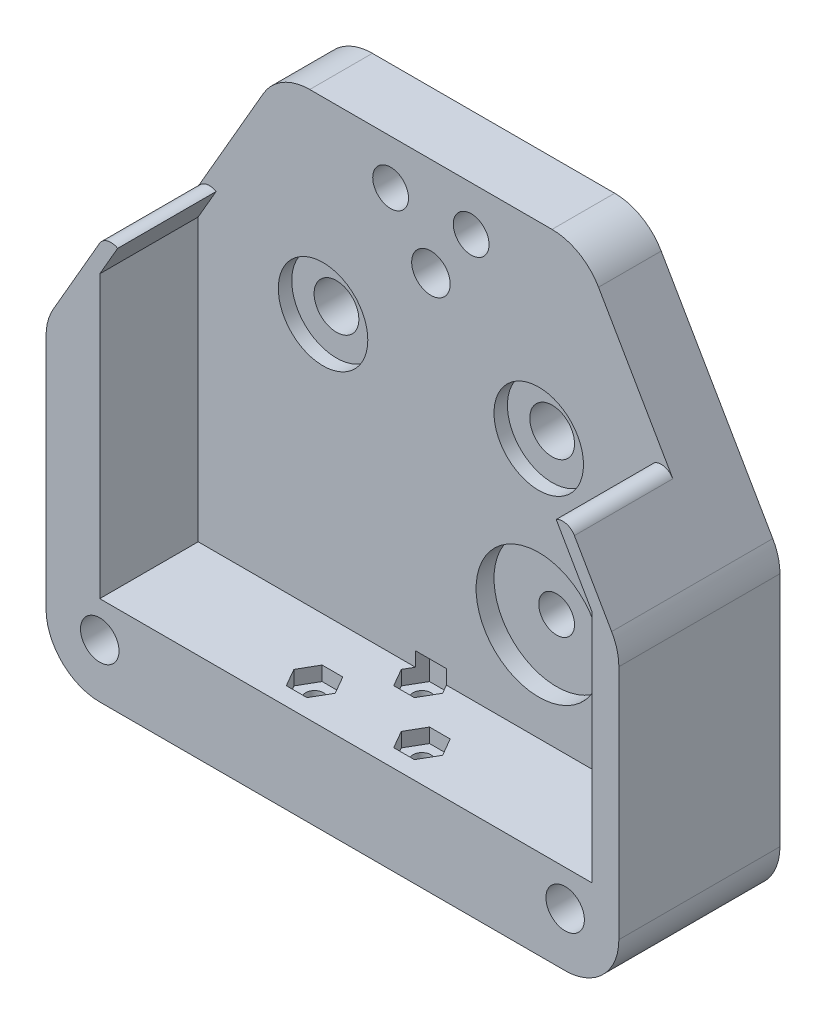
SolidWorks part; units mm, degrees
material "ABS"
ref_plane "Спереди" through (0, 0, 0) normal (0, 0, 1) x (1, 0, 0)
ref_plane "Сверху" through (0, 0, 0) normal (0, 1, 0) x (1, 0, 0)
ref_plane "Справа" through (0, 0, 0) normal (1, 0, 0) x (0, 0, -1)
sketch "Эскиз1" plane through (0, 0, 0) normal (0, 0, 1) x (1, 0, 0)
  line L0 (0, 0) -> (64, 0)
  line L1 (64, 0) -> (64, 34.0192)
  line L2 (64, 34.0192) -> (49, 60)
  line L3 (49, 60) -> (15, 60)
  line L4 (15, 60) -> (0, 34.02)
  line L5 (0, 34.02) -> (0, 0)
  dimension "D1" = 64
  dimension "D2" = 60
  dimension "D3" = 120
  dimension "D4" = 34
  dimension "D5" = 30
  dimension "D6" = 34.02
extrude "Бобышка-Вытянуть1" add sketch "Эскиз1" along normal blind 7
sketch "Эскиз3" plane through (0, 0, 7) normal (0, 0, 1) x (1, 0, 0)
  line L0 (0, 0) -> (64, 0)
  line L1 (64, 0) -> (64, 34.0192)
  line L2 (64, 34.0192) -> (58.2904, 43.9086)
  line L3 (64, 34.0192) -> (49, 60) construction
  line L4 (58.2904, 43.9086) -> (57, 43.1636)
  line L5 (57, 43.1636) -> (61, 36.2354)
  line L6 (61, 36.2354) -> (61, 10)
  line L7 (61, 10) -> (6, 10)
  line L8 (6, 10) -> (6, 41.4321)
  line L9 (6, 41.4321) -> (8, 44.8961)
  line L10 (8, 44.8961) -> (6.7097, 45.6412)
  line L11 (15, 60) -> (0, 34.02) construction
  line L12 (6.7097, 45.6412) -> (0, 34.02)
  line L13 (0, 34.02) -> (0, 0)
  dimension "D1" = 55
  dimension "D2" = 6
  dimension "D3" = 10
  dimension "D4" = 4
  dimension "D5" = 8
  dimension "D6" = 1.49
  dimension "D7" = 1.49
extrude "Бобышка-Вытянуть2" add sketch "Эскиз3" along normal blind 11
fillet "Скругление1" radius 6 6 edges at (64, 34.0192, 9) (49, 60, 3.5) (15, 60, 3.5) (0, 34.02, 9) (0, 0, 9) (64, 0, 9)
fillet "Скругление2" radius 1.49 2 edges at (58.2904, 43.9086, 12.5) (6.7097, 45.6412, 12.5)
hole_wizard "Зенковка для  винта с плоской головкой M44" positions "Эскиз13" profile "Эскиз14" countersink size "M4" standard "Ansi Metric" end condition through all
sketch "Эскиз13" plane through (0, 0, 0) normal (0, 0, -1) x (-1, 0, 0)
  line L3 (-32, 62.7004) -> (-32, -1.1162) construction
  line L5 (-45.5359, 60) -> (-18.4641, 60) construction
  line L6 (-6, 0) -> (-58, 0) construction
  line L7 (-64, 6) -> (-64, 32.4115) construction
  point P0 (-5.9999, 6)
  point P2 (-58, 6)
  point P4 (-32, 49)
  point P34 (-32, 60)
  dimension "D1" = 11
  dimension "D2" = 6
  dimension "D3" = 6
sketch "Эскиз14" plane through (5.9999, 6, 0) normal (1, 0, 0) x (0, 1, 0)
  line L0 (0, 0) -> (0, 18)
  line L1 (0, 18) -> (2.15, 18)
  line L2 (2.15, 18) -> (2.15, 2.2)
  line L3 (2.15, 2.2) -> (4.35, 0)
  line L5 (4.35, 0) -> (0, 0)
  line L6 (-2.15, 2.2) -> (-4.35, 0) construction
  line L11 (0, -3.8306) -> (0, 22.0892) construction
  dimension "Диаметр сквозного отверстия" = 4.3
  dimension "Глубина сквозного отверстия" = 18
  dimension "Диаметр передней зенковки" = 8.7
  dimension "Угол передней зенковки" = 90
hole_wizard "Отверстия под штифты Ø4.0 мм2" positions "Эскиз19" profile "Эскиз20" hole size "Ø4.0" standard "Ansi Metric" end condition through all
sketch "Эскиз19" plane through (0, 0, 0) normal (0, 0, -1) x (-1, 0, 0)
  line L0 (-45.5359, 60) -> (-18.4641, 60) construction
  line L1 (-64, 6) -> (-64, 32.4115) construction
  line L8 (-32, 62.4273) -> (-32, -3.8376) construction
  point P0 (-36.5, 55)
  point P2 (-27.4999, 55)
  point P94 (-32, 60)
  dimension "D1" = 5
  dimension "D2" = 27.5
sketch "Эскиз20" plane through (36.5, 55, 0) normal (1, 0, 0) x (0, 1, 0)
  line L0 (0, 0) -> (0, 18)
  line L1 (0, 18) -> (2, 18)
  line L2 (2, 18) -> (2, 0)
  line L5 (2, 0) -> (0, 0)
  line L11 (0, -3.866) -> (0, 11.4564) construction
  dimension "Диаметр сквозного отверстия" = 4
  dimension "Глубина сквозного отверстия" = 18
hole_wizard "Отверстия под штифты Ø5.0 мм1" positions "Эскиз21" profile "Эскиз22" hole size "Ø5.0" standard "Ansi Metric" end condition through all
sketch "Эскиз21" plane through (0, 0, 0) normal (0, 0, -1) x (-1, 0, 0)
  line L0 (-45.5359, 60) -> (-18.4641, 60) construction
  line L1 (-64, 6) -> (-64, 32.4115) construction
  line L2 (-32, 62.1722) -> (-32, -3.1086) construction
  point P0 (-44.05, 39)
  point P2 (-19.9499, 39)
  point P18 (-32, 60)
  dimension "D1" = 21
  dimension "D2" = 19.95
sketch "Эскиз22" plane through (44.05, 39, 0) normal (1, 0, 0) x (0, 1, 0)
  line L0 (0, 0) -> (0, 18)
  line L1 (0, 18) -> (2.5, 18)
  line L2 (2.5, 18) -> (2.5, 0)
  line L5 (2.5, 0) -> (0, 0)
  line L11 (0, -6.35) -> (0, 13.5001) construction
  dimension "Диаметр сквозного отверстия" = 5
  dimension "Глубина сквозного отверстия" = 18
ref_plane "Плоскость2" through (0, 10, 0) normal (0, -1, 0) x (-1, 0, 0)
hole_wizard "Отверстия под штифты Ø4.0 мм3" positions "Эскиз52" profile "Эскиз53" hole size "Ø4.0" standard "Ansi Metric" end condition through all
sketch "Эскиз52" plane through (0, 0, 7) normal (0, 0, 1) x (1, 0, 0)
  line L0 (64, 6) -> (64, 32.4115) construction
  line L1 (6, 0) -> (58, 0) construction
  point P0 (44.05, 21)
  dimension "D1" = 19.95
  dimension "D2" = 21
sketch "Эскиз53" plane through (44.05, 21, 7) normal (1, 0, 0) x (0, -1, 0)
  line L0 (0, 0) -> (0, 7)
  line L1 (0, 7) -> (2, 7)
  line L2 (2, 7) -> (2, 0)
  line L5 (2, 0) -> (0, 0)
  line L11 (0, -6.35) -> (0, 24.92) construction
  dimension "Диаметр сквозного отверстия" = 4
  dimension "Глубина сквозного отверстия" = 7
sketch "Эскиз54" plane through (0, 0, 7) normal (0, 0, 1) x (1, 0, 0)
  line L0 (64, 6) -> (64, 32.4115) construction
  line L1 (6, 0) -> (58, 0) construction
  circle A0 centre (44.05, 21) radius 7
  dimension "D1" = 14
  dimension "D2" = 19.95
  dimension "D3" = 21
extrude "Вырез-Вытянуть5" cut sketch "Эскиз54" against normal blind 2
sketch "Эскиз55" plane through (0, 0, 7) normal (0, 0, 1) x (1, 0, 0)
  circle A0 centre (19.9499, 39) radius 5
  circle A1 centre (19.9499, 39) radius 2.5 construction
  circle A2 centre (44.05, 39) radius 5
  circle A3 centre (44.05, 39) radius 2.5 construction
  dimension "D1" = 10
  dimension "D2" = 10
extrude "Вырез-Вытянуть9" cut sketch "Эскиз55" against normal blind 1.5
hole_wizard "Сверло под метчик  спиральное M2.21" positions "Эскиз56" profile "Эскиз57" hole size "M2.2x0.45" standard "Ansi Metric"
sketch "Эскиз56" plane through (0, 0, 0) normal (0, -1, 0) x (-1, 0, 0)
  line L0 (-6, -18) -> (-58, -18) construction
  line L1 (-32, -19.1422) -> (-32, -5.5593) construction
  line L3 (-6, -18) -> (-6, 0) construction
  point P0 (-26, -14)
  point P2 (-38, -14)
  point P15 (-32, -18)
  dimension "D1" = 4
  dimension "D2" = 20
sketch "Эскиз57" plane through (26, 0, 14) normal (1, 0, 0) x (0, 0, -1)
  line L0 (0, 0) -> (0, 10.6009)
  line L1 (0, 10.6009) -> (1, 10)
  line L2 (1, 10) -> (1, 0)
  line L5 (1, 0) -> (0, 0)
  line L10 (0, 10.6009) -> (-1, 10) construction
  line L11 (0, -6.35) -> (0, 14.5802) construction
  dimension "Диаметр отверстия" = 2
  dimension "Глубина отверстия" = 10
  dimension "Угол заточки сверла" = 118
sketch "Эскиз58" plane through (0, 10, 0) normal (0, 1, 0) x (1, 0, 0)
  line L0 (26, -10.8602) -> (26, -17.0191) construction
  line L1 (28.3094, -14) -> (27.1547, -12)
  line L2 (27.1547, -12) -> (24.8453, -12)
  line L3 (24.8453, -12) -> (23.6906, -14)
  line L4 (23.6906, -14) -> (24.8453, -16)
  line L5 (24.8453, -16) -> (27.1547, -16)
  line L6 (27.1547, -16) -> (28.3094, -14)
  line L9 (38, -10.8602) -> (38, -17.0191) construction
  line L10 (40.3094, -14) -> (39.1547, -12)
  line L11 (39.1547, -12) -> (36.8453, -12)
  line L12 (36.8453, -12) -> (35.6906, -14)
  line L13 (35.6906, -14) -> (36.8453, -16)
  line L14 (36.8453, -16) -> (39.1547, -16)
  line L15 (39.1547, -16) -> (40.3094, -14)
  circle A0 centre (26, -14) radius 2 construction
  circle A1 centre (38, -14) radius 2 construction
  dimension "D1" = 4
  dimension "D2" = 30
  dimension "D3" = 4
  dimension "D4" = 30
extrude "Вырез-Вытянуть11" cut sketch "Эскиз58" against normal blind 1.6
hole_wizard "Сверло под метчик  спиральное M2.22" positions "Эскиз59" profile "Эскиз60" hole size "M2.2x0.45" standard "Ansi Metric"
sketch "Эскиз59" plane through (0, 0, 0) normal (0, -1, 0) x (-1, 0, 0)
  line L0 (-6, -18) -> (-58, -18) construction
  line L1 (-58, 0) -> (-58, -18) construction
  point P0 (-32, -8)
  dimension "D1" = 10
  dimension "D2" = 26
sketch "Эскиз60" plane through (32, 0, 8) normal (1, 0, 0) x (0, 0, -1)
  line L0 (0, 0) -> (0, 10.6009)
  line L1 (0, 10.6009) -> (1, 10)
  line L2 (1, 10) -> (1, 0)
  line L5 (1, 0) -> (0, 0)
  line L10 (0, 10.6009) -> (-1, 10) construction
  line L11 (0, -6.35) -> (0, 21.1048) construction
  dimension "Диаметр отверстия" = 2
  dimension "Глубина отверстия" = 10
  dimension "Угол заточки сверла" = 118
sketch "Эскиз61" plane through (0, 10, 0) normal (0, 1, 0) x (1, 0, 0)
  line L0 (32, -5.2203) -> (32, -10.1362) construction
  line L1 (34.3094, -8) -> (33.1547, -6)
  line L2 (33.1547, -6) -> (30.8453, -6)
  line L3 (30.8453, -6) -> (29.6906, -8)
  line L4 (29.6906, -8) -> (30.8453, -10)
  line L5 (30.8453, -10) -> (33.1547, -10)
  line L6 (33.1547, -10) -> (34.3094, -8)
  circle A0 centre (32, -8) radius 2 construction
  dimension "D1" = 4
  dimension "D2" = 30
extrude "Вырез-Вытянуть12" cut sketch "Эскиз61" against normal blind 1.6
sketch "Эскиз62" plane through (0, 10, 0) normal (0, -1, 0) x (-1, 0, 0)
  line L1 (-29.6906, -8) -> (-30.8453, -6)
  line L2 (-30.8453, -6) -> (-33.1547, -6)
  line L3 (-33.1547, -6) -> (-34.3094, -8)
  line L4 (-34.3094, -8) -> (-33.1547, -10)
  line L5 (-33.1547, -10) -> (-30.8453, -10)
  line L6 (-30.8453, -10) -> (-29.6906, -8)
  line L8 (-32, -5.0947) -> (-32, -10.6745) construction
  circle A0 centre (-32, -8) radius 2 construction
  circle A1 centre (-32, -8) radius 1 construction
  dimension "D1" = 4
  dimension "D2" = 30
extrude "Вырез-Вытянуть13" cut sketch "Эскиз62" against normal blind 1.6
